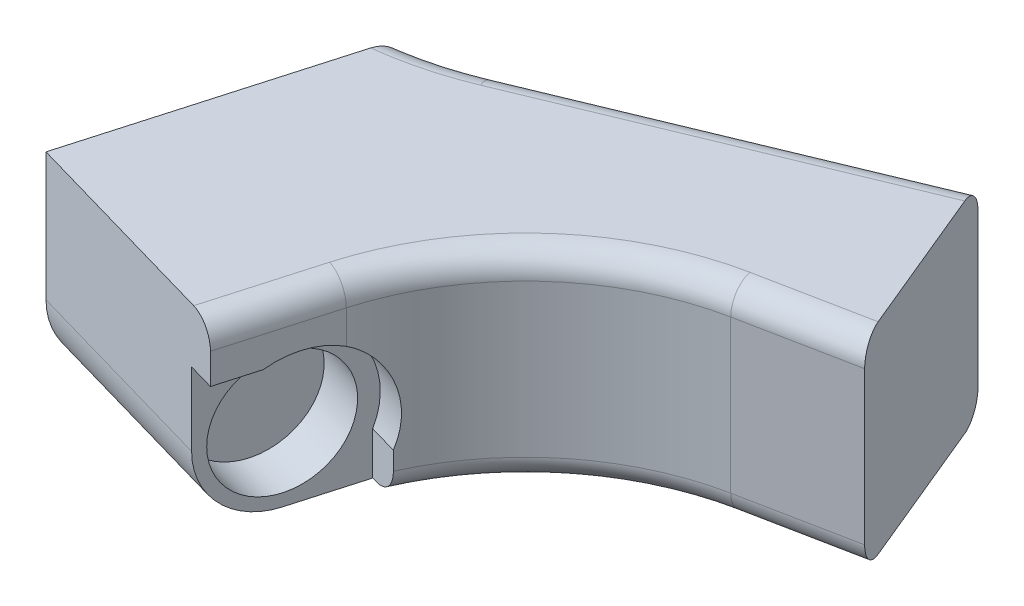
SolidWorks part; units mm, degrees
ref_plane "Спереди" through (0, 0, 0) normal (0, 0, 1) x (1, 0, 0)
ref_plane "Сверху" through (0, 0, 0) normal (0, 1, 0) x (1, 0, 0)
ref_plane "Справа" through (0, 0, 0) normal (1, 0, 0) x (0, 0, -1)
sketch "Эскиз2" plane through (0, 0, 0) normal (0, 1, 0) x (1, 0, 0)
  line L0 (-37.0181, 71.2336) -> (-60.5171, 61.5)
  line L1 (-69.8478, 61.5) -> (-60.5171, 61.5)
  line L3 (-53.9856, 37.3604) -> (-49.6599, 36.12)
  line L4 (-49.6599, 36.12) -> (-50.3578, 33.6863)
  line L5 (-50.3578, 33.6863) -> (-54.6834, 34.9267)
  line L17 (-62.1563, 39.7033) -> (-61.1916, 43.0677)
  line L24 (-61.1916, 43.0677) -> (-57.3465, 41.9652)
  line L25 (-57.3465, 41.9652) -> (-60.6542, 30.43)
  line L26 (-20.9839, 57.3097) -> (-21.1984, 57.2209)
  line L28 (-17, 57.5) -> (-17.2322, 57.5)
  line L30 (-60.6542, 30.43) -> (-64.4992, 31.5326)
  line L31 (-75.5193, 43.5351) -> (-75.0386, 43.3973)
  line L32 (-75.0386, 43.3973) -> (-74.0739, 46.7617)
  line L34 (-39.6579, 36.893) -> (-40.6226, 33.5286)
  line L35 (-74.0739, 46.7617) -> (-70.2289, 45.6591)
  line L36 (-37.2122, 54.0355) -> (-37.1146, 53.5451) construction
  line L37 (-55.8479, 29.0519) -> (-52.5402, 40.587)
  line L39 (-37.1146, 53.5451) -> (-52.0151, 50.5813)
  line L41 (-39.1205, 24.2554) -> (-42.9655, 25.3579)
  line L43 (-39.6579, 36.893) -> (-35.8129, 35.7905)
  line L45 (-40.6226, 33.5286) -> (-42.0008, 28.7223)
  line L46 (-42.0008, 28.7223) -> (-42.9655, 25.3579)
  line L47 (-39.1205, 24.2554) -> (-38.1558, 27.6198)
  line L49 (-38.1558, 27.6198) -> (-36.7776, 32.4261)
  line L51 (-36.7776, 32.4261) -> (-35.8129, 35.7905)
  line L52 (-36.7776, 32.4261) -> (-40.6226, 33.5286)
  line L53 (-42.0008, 28.7223) -> (-38.1558, 27.6198)
  line L54 (-26.4853, 38.5) -> (-35.0359, 38.5)
  line L55 (-35.8129, 35.7905) -> (-35.0359, 38.5)
  line L56 (-78, 34.8837) -> (-75.5193, 43.5351)
  line L57 (-71.1936, 42.2947) -> (-78, 44.2464)
  line L59 (-70.2289, 45.6591) -> (-73.5365, 34.124)
  line L60 (-73.5365, 34.124) -> (-77.3816, 35.2265)
  line L62 (-75.0386, 43.3973) -> (-76.4168, 38.5909)
  line L63 (-76.4168, 38.5909) -> (-72.5718, 37.4884)
  line L64 (-76.4168, 38.5909) -> (-77.3816, 35.2265)
  line L65 (-74.0739, 46.7617) -> (-69.8478, 61.5)
  line L66 (-70.7314, 58.4185) -> (-71.212, 58.5563) construction
  line L67 (-71.212, 58.5563) -> (-70.3679, 61.5)
  line L68 (-70.3679, 61.5) -> (-78, 61.5)
  line L69 (-71.212, 58.5563) -> (-75.5193, 43.5351)
  line L70 (-64.4992, 31.5326) -> (-62.1563, 39.7033)
  line L71 (-54.6834, 34.9267) -> (-53.9856, 37.3604)
  line L73 (-51.6069, 36.6783) -> (-51.6035, 36.6902)
  line L74 (-51.6035, 36.6902) -> (-55.6644, 37.8547)
  line L75 (-48.6952, 39.4844) -> (-52.0028, 27.9493)
  line L77 (-52.0028, 27.9493) -> (-55.8479, 29.0519)
  line L83 (-73.5365, 34.124) -> (-64.4992, 31.5326)
  line L84 (-56.145, 37.9925) -> (-52.4581, 50.8502)
  line L85 (-52.0028, 27.9493) -> (-42.9655, 25.3579)
  line L86 (-55.6644, 37.8547) -> (-52.0151, 50.5813)
  line L87 (-56.145, 37.9925) -> (-58.3078, 38.6127)
  line L88 (-26.4853, 55.6595) -> (-26.4853, 38.5)
  line L89 (-37.0181, 71.2336) -> (-30.4515, 55.3803)
  line L91 (-52.5402, 40.587) -> (-48.6952, 39.4844)
  line L93 (-37.2122, 54.0355) -> (-21.1984, 57.2209)
  line L94 (-37.2122, 54.0355) -> (-52.4117, 51.0122)
  line L95 (-52.4581, 50.8502) -> (-52.4117, 51.0122)
  line L96 (-37.1146, 53.5451) -> (-17.2322, 57.5)
  point P54 (-75.5193, 43.5351)
sketch "Эскиз3" plane through (0, 0, 0) normal (0, 1, 0) x (1, 0, 0)
  line L0 (-30.4515, 55.3803) -> (-37.0181, 71.2336)
  line L1 (-37.0181, 71.2336) -> (-60.5171, 61.5)
  line L3 (-70.8514, 58) -> (-77.3816, 35.2265)
  line L4 (-77.3816, 35.2265) -> (-73.5365, 34.124)
  line L5 (-73.5365, 34.124) -> (-70.2289, 45.6591)
  line L6 (-70.2289, 45.6591) -> (-61.1916, 43.0677)
  line L7 (-61.1916, 43.0677) -> (-64.4992, 31.5326)
  line L8 (-64.4992, 31.5326) -> (-60.6542, 30.43)
  line L14 (-70.8514, 58) -> (-68.9668, 58)
  line L18 (-60.5171, 61.5) -> (-68.9668, 58)
  line L22 (-56.145, 37.9925) -> (-52.4581, 50.8502) construction
  line L23 (-56.0106, 38.4612) -> (-58.4913, 29.8099)
  line L24 (-60.6542, 30.43) -> (-58.4913, 29.8099)
  line L28 (-37.2122, 54.0355) -> (-52.4117, 51.0122) construction
  line L29 (-30.4515, 55.3803) -> (-39.6058, 53.5594)
  arc A4 (-56.0106, 38.4612) -> (-39.6058, 53.5594) centre (-35.4286, 32.5594) cw
extrude "Бобышка-Вытянуть1" add sketch "Эскиз3" against normal blind 6 and the other way blind 10.5 contours L0 L1 L3 L4 L5 L6 L7 L8 region at (-54.569, 0, -53.0174)
fillet "Скругление1" radius 25 1 edges at (-68.9668, 2.25, -58)
fillet "Скругление2" radius 2 10 edges at (-51.0429, 10.5, -65.4243) (-51.0429, -6, -65.4243) (-57.251, -6, -34.1355) (-35.0287, -6, -54.4699) (-57.251, 10.5, -34.1355) (-35.0287, 10.5, -54.4699) (-49.9284, -6, -48.314) (-49.9284, 10.5, -48.314) (-67.9109, 10.5, -58.6333) (-67.9109, -6, -58.6333)
sketch "Эскиз4" plane through (-67.9537, 0, -19.4854) normal (0.9613, 0, 0.2756) x (0.2756, 0, -0.9613)
  line L0 (12.5327, -6) -> (18.5327, -6)
  line L2 (18.5327, -6) -> (18.5327, 0)
  line L3 (12.5327, 0) -> (12.5327, -6)
  line L4 (12.5327, -6) -> (18.5327, -6)
  circle A0 centre (18.5327, 0) radius 5
  circle A1 centre (18.5327, 0) radius 6
  line M17 (24.5327, -6) -> (12.5327, -6)
  line M18 (12.5327, -6) -> (12.5327, 10.5)
extrude "Вырез-Вытянуть1" cut sketch "Эскиз4" against normal through all and the other way blind 4 contours A0 | A1 M18 M17 region at (-64.1298, -4.6598, -32.8209) region at (-63.7924, 3.4355, -33.9977)
sketch "Эскиз5" plane through (-61.9458, 0, -17.7627) normal (0.9613, 0, 0.2756) x (0.2756, 0, -0.9613)
  line L0 (12.5327, -6) -> (12.5327, 0)
  line L1 (12.5327, 8.5) -> (12.5327, -4) construction
  line L3 (36.6593, 0) -> (21.0327, 0) construction
  line L4 (16.0327, 6) -> (12.5327, 6)
  line L5 (12.5327, 6) -> (12.5327, 0)
  line L6 (12.5327, -6) -> (18.5327, -6)
  line L9 (24.5327, -6) -> (18.5327, -6)
  line L10 (24.5327, -2.5) -> (24.5327, -6)
  arc A2 (24.5327, -2.5) -> (16.0327, 6) centre (18.5327, 0) ccw
  line M1 (12.5327, 8.5) -> (12.5327, -4)
  line M3 (21.5327, -4) -> (21.5327, 8.5)
extrude "Вырез-Вытянуть2" cut sketch "Эскиз5" against normal blind 2.25 and the other way through all contours L6 | L5 M1 | A2 L4 M3 M1 | L10 A2 L9 M3 region at (-56.8608, -0.0843, -35.4964)
sketch "Эскиз6" plane through (-67.9537, 0, -19.4854) normal (-0.9613, 0, -0.2756) x (-0.2756, 0, 0.9613)
  line L0 (-16.0327, 0) -> (-21.0327, 0) construction
  line L1 (-24.5327, 10.5) -> (-24.5327, -6)
  line L2 (-24.5327, -6) -> (-18.5327, -6)
  line L4 (-12.5327, 0) -> (-12.5327, 10.5)
  line L5 (-12.5327, 10.5) -> (-24.5327, 10.5)
  arc A0 (-18.5327, -6) -> (-12.5327, 0) centre (-18.5327, 0) ccw
extrude "Бобышка-Вытянуть2" add sketch "Эскиз6" along normal up to surface (9.4015 mm away) up to face at (-73.2609, 0, -35.0852)
